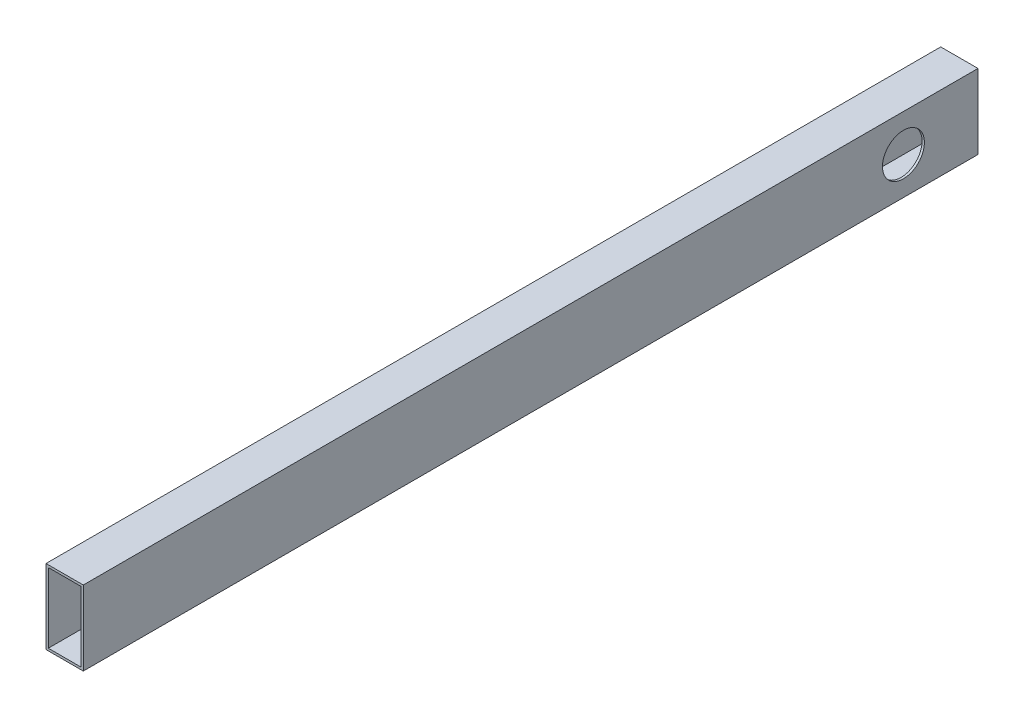
SolidWorks part; units mm, degrees
material "6061-T4 (SS)"
ref_plane "Front Plane" through (0, 0, 0) normal (0, 0, 1) x (1, 0, 0)
ref_plane "Top Plane" through (0, 0, 0) normal (0, 1, 0) x (1, 0, 0)
ref_plane "Right Plane" through (0, 0, 0) normal (1, 0, 0) x (0, 0, -1)
sketch "Sketch1" plane through (0, 0, 0) normal (0, 0, 1) x (1, 0, 0)
  line L0 (1.5875, 49.2125) -> (23.8125, 49.2125)
  line L5 (0, 0) -> (25.4, 0)
  line L6 (0, 0) -> (0, 50.8)
  line L7 (0, 50.8) -> (25.4, 50.8)
  line L8 (25.4, 0) -> (25.4, 50.8)
  line L13 (23.8125, 1.5875) -> (23.8125, 49.2125)
  line L14 (1.5875, 1.5875) -> (23.8125, 1.5875)
  line L15 (1.5875, 1.5875) -> (1.5875, 49.2125)
  dimension "D1" = 25.4
  dimension "D2" = 1.5875
  dimension "D3" = 50.8
extrude "Boss-Extrude1" add sketch "Sketch1" along normal blind 609.6
sketch "Sketch2" plane through (0, 0, 0) normal (-1, 0, 0) x (0, 0, 1)
  line L0 (609.6, 50.8) -> (609.6, 0) construction
  line L1 (609.6, 50.8) -> (0, 50.8) construction
  circle A16 centre (558.8, 38.1) radius 2.4892
  circle A17 centre (533.4, 38.1) radius 2.4892
  circle A18 centre (508, 38.1) radius 2.4892
  circle A19 centre (482.6, 38.1) radius 2.4892
  circle A21 centre (558.8, 12.7) radius 2.4892
  circle A22 centre (533.4, 12.7) radius 2.4892
  circle A23 centre (508, 12.7) radius 2.4892
  circle A24 centre (482.6, 12.7) radius 2.4892
  circle A26 centre (584.2, 12.7) radius 2.4892
  circle A29 centre (584.2, 38.1) radius 2.4892
  circle A30 centre (457.2, 38.1) radius 2.4892 [skipped]
  circle A31 centre (457.2, 12.7) radius 2.4892 [skipped]
  dimension "D4" = 25.4
  dimension "D5" = 6
  dimension "D6" = 2
  dimension "D1" = 4.9784
  dimension "D7" = 12.7
  dimension "D2" = 25.4
  dimension "D3" = 25.4
extrude "Cut-Extrude1" cut sketch "Sketch2" against normal up to next
sketch "Sketch3" plane through (0, 0, 0) normal (-1, 0, 0) x (0, 0, 1)
  line L0 (609.6, 25.4) -> (0, 25.4) construction
  line L1 (609.6, 50.8) -> (609.6, 0) construction
  line L2 (0, 50.8) -> (0, 0) construction
  circle A0 centre (50.8, 25.4) radius 14.2875
  dimension "D1" = 28.575
  dimension "D2" = 50.8
extrude "Cut-Extrude2" cut sketch "Sketch3" against normal through all
